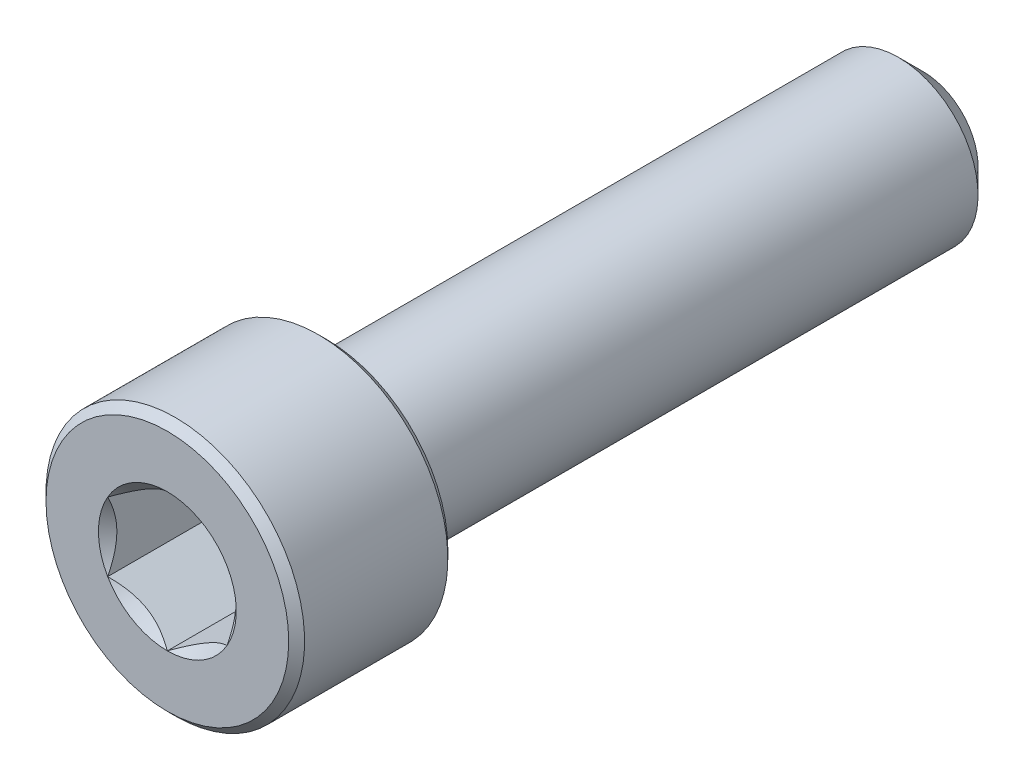
SolidWorks part; units mm, degrees
ref_plane "Front Plane" through (0, 0, 0) normal (0, 0, 1) x (1, 0, 0)
ref_plane "Top Plane" through (0, 0, 0) normal (0, 1, 0) x (1, 0, 0)
ref_plane "Right Plane" through (0, 0, 0) normal (1, 0, 0) x (0, 0, -1)
sketch "Sketch1" plane through (0, 0, 0) normal (1, 0, 0) x (0, 0, -1)
  line L0 (-19, 0) -> (19, 0) construction
  line L1 (19, 0) -> (19, 2.75) construction
  line L2 (19, 2.75) -> (17.75, 4) construction
  line L3 (17.75, 4) -> (18.0625, 4) construction
  line L4 (18.0625, 4) -> (-11, 4) construction
  line L5 (-11, 4) -> (-11, 6.5) construction
  line L6 (-11, 6.5) -> (-19, 6.5) construction
  line L7 (-19, 6.5) -> (-19, 0) construction
  line L8 (19, 2.75) -> (19, 4) construction
  line L9 (18.9219, 4.1353) -> (19.5469, 3.0528) construction
  line L10 (19.5469, 3.0528) -> (20.1719, 4.1353) construction
  line L11 (20.1719, 4.1353) -> (18.9219, 4.1353) construction
  line L12 (19.5469, 4.1353) -> (19.5469, 4) construction
  line L13 (19.5469, 3.0528) -> (19.5469, 3.1881) construction
  line L14 (19.4688, 3.1881) -> (19.625, 3.1881) construction
  line L15 (19, 4) -> (20.0938, 4) construction
  line L16 (18.9609, 4.0677) -> (20.1328, 4.0677) construction
  line L17 (19, 0) -> (19, -4) construction
  line L18 (-11.4, 6.5) -> (-11, 6.1) construction
  line L19 (-18.6, 6.5) -> (-19, 6.1) construction
  line L20 (-11, 4) -> (-11, 0) construction
  line L21 (-11, 2) -> (-1, 2) construction
  line L22 (-1, 2) -> (9, 2) construction
  line L23 (9, 2) -> (19, 2) construction
  line L24 (-1, 2) -> (-1, 4) construction
  line L25 (-1, 4) -> (-1, 6.5) construction
  line L26 (9, 2) -> (9, 6.5) construction
  point P0 (-19, 3)
  point P3 (15.875, 4)
  point P4 (0, 0)
  point P18 (9, 4)
  point P22 (19.5469, 3.1881)
  point P24 (18.0625, 4)
  point P25 (19.5469, 4)
  point P28 (19.5469, 4.0677)
  point P29 (15.875, -4)
  point P30 (-1, 4)
  point P31 (-15, 6.5)
  point P37 (-12.4, 6.5)
  point P38 (-18.4, 6.5)
  point P45 (-1, 2)
  point P46 (9, 2)
  dimension "D1" = 45
  dimension "D2" = 0.1562
  dimension "D3" = 1.25
  dimension "D7" = 0.4
  dimension "D8" = 0.4
  dimension "D9" = 0.4
  dimension "D10" = 0.2
  dimension "D11" = 1
  dimension "Drive Size" = 6
  dimension "Head Diameter" = 13
  dimension "Head Height" = 8
  dimension "Thread Pitch" = 1.25
  dimension "Thread Major Diameter" = 8
  dimension "Length" = 30
  dimension "D12" = 0.9375
  dimension "D4" = 3.125
sketch "Sketch2" plane through (0, 0, 0) normal (1, 0, 0) x (0, 0, -1)
  line L0 (-19, 0) -> (-19, 6.1)
  line L1 (-18.6, 6.5) -> (-11.4, 6.5)
  line L2 (-11, 6.1) -> (-11, 4)
  line L3 (-11, 4) -> (17.75, 4)
  line L4 (17.75, 4) -> (19, 2.75)
  line L5 (19, 2.75) -> (19, 0)
  line L6 (-11.4, 6.5) -> (-11, 6.1) construction
  line L7 (19, 0) -> (-19, 0)
  line L8 (-18.6, 6.5) -> (-19, 6.1) construction
  line L9 (-11.4, 6.5) -> (-11, 6.1)
  line L10 (-18.6, 6.5) -> (-19, 6.1)
revolve "Revolve1" add sketch "Sketch2" angle 360 about L7
sketch "Sketch3" plane through (0, 0, 19) normal (0, 0, 1) x (1, 0, 0)
  line L1 (3, -1.7321) -> (3, 1.7321)
  line L2 (3, 1.7321) -> (0, 3.4641)
  line L3 (0, 3.4641) -> (-3, 1.7321)
  line L4 (-3, 1.7321) -> (-3, -1.7321)
  line L5 (-3, -1.7321) -> (0, -3.4641)
  line L6 (0, -3.4641) -> (3, -1.7321)
  circle A0 centre (0, 0) radius 3 construction
extrude "Cut-Extrude1" cut sketch "Sketch3" against normal offset from surface (7 mm away) 1 up to face at (0, 6.1, 11)
sketch "Sketch4" plane through (0, 0, 19) normal (0, 0, 1) x (1, 0, 0)
  circle A0 centre (0, 0) radius 3.4641
extrude "Cut-Extrude2" cut sketch "Sketch4" against normal up to vertex (4 mm away) draft 45 up to point (0, 6.5, 15)
ref_plane "Plane1" [suppressed] through (0, 0, -18.0625) normal (0, 0, 1) x (1, 0, 0)
split "Split1" [suppressed] bodies to split 106
sketch "Sketch6" [suppressed] plane through (0, 0, -19) normal (0, 0, -1) x (-1, 0, 0)
  circle A0 centre (0, 0) radius 4
curve "Helix/Spiral1" [suppressed] pitch 1.25 height 31.4375 turns 25.15
sketch "Sketch7" [suppressed] plane through (0, 0, 0) normal (1, 0, 0) x (0, 0, -1)
  line L0 (18.9609, 4.0677) -> (20.1328, 4.0677)
  line L1 (20.1328, 4.0677) -> (19.625, 3.1881)
  line L2 (19.625, 3.1881) -> (19.4688, 3.1881)
  line L3 (19.4688, 3.1881) -> (18.9609, 4.0677)
sweep "Cut-Sweep1" [suppressed] cut profiles "Sketch7" path "Helix/Spiral1"
sketch "Sketch8" [suppressed] plane through (0, 0, 11) normal (0, 0, -1) x (-1, 0, 0)
  circle A0 centre (0, 0) radius 4
extrude "Boss-Extrude1" [suppressed] add sketch "Sketch8" along normal through all draft 45
equation "\"D2@Sketch1\" = \"Thread Pitch@Sketch1\" / 8"
equation "\"D3@Sketch1\"= \"Thread Pitch@Sketch1\""
equation "\"D4@Helix/Spiral1\" = \"Thread Pitch@Sketch1\""
equation "\"D7@Sketch1\" = \"Head Height@Sketch1\" * .05"
equation "\"D8@Sketch1\"=\"D7@Sketch1\""
equation "\"D9@Sketch1\"=\"D7@Sketch1\""
equation "\"D10@Sketch1\"=\"D7@Sketch1\"/2"
equation "\"D11@Sketch1\"=\"D10@Sketch1\"*5"
equation "\"D4@Sketch1\"=\"Thread Pitch@Sketch1\"*2.5"
equation "\"D12@Sketch1\"=\"Thread Pitch@Sketch1\"*.75"
